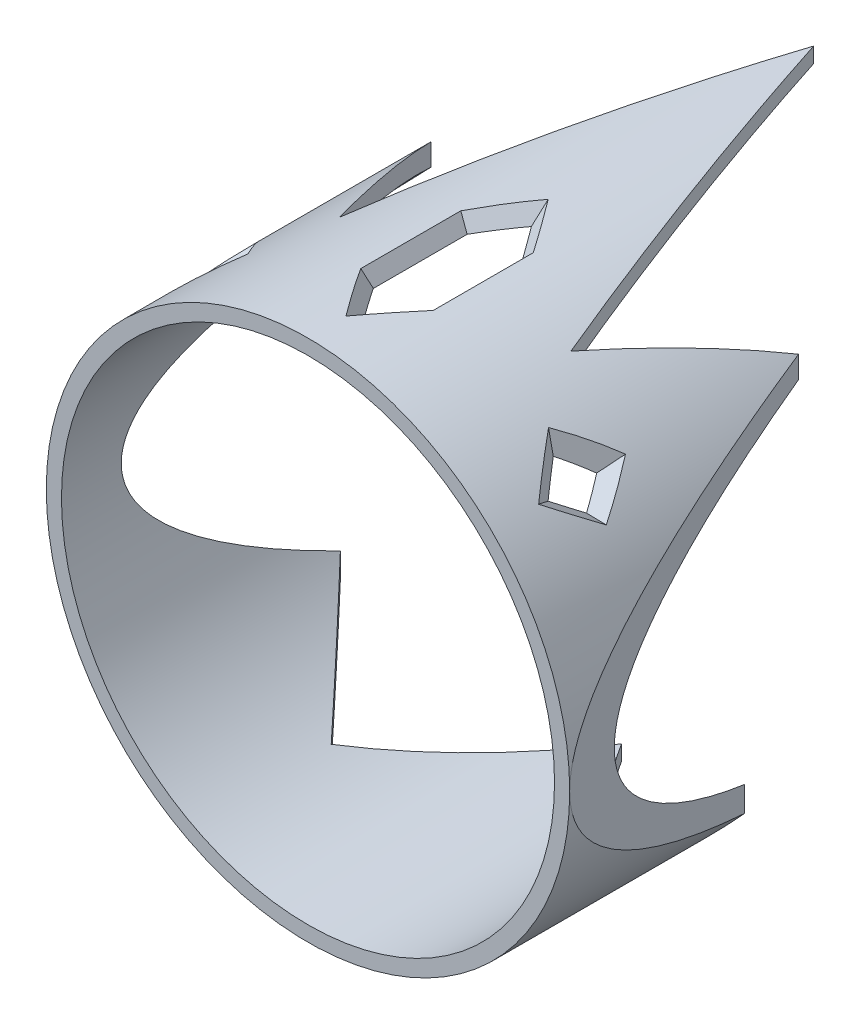
SolidWorks part; units mm, degrees
ref_plane "Alzado" through (0, 0, 0) normal (0, 0, 1) x (1, 0, 0)
ref_plane "Planta" through (0, 0, 0) normal (0, 1, 0) x (1, 0, 0)
ref_plane "Vista lateral" through (0, 0, 0) normal (1, 0, 0) x (0, 0, -1)
sketch "Croquis1" plane through (0, 0, 0) normal (0, 0, 1) x (1, 0, 0)
  circle A0 centre (0, 0) radius 97.5
  circle A1 centre (0, 0) radius 103.5
  dimension "D1" = 195
  dimension "D2" = 6
extrude "Base" add sketch "Croquis1" along normal blind 200
sketch "Croquis2" plane through (0, 0, 0) normal (0, 1, 0) x (1, 0, 0)
  line L3 (-103.5, -200) -> (103.5, -200)
  line L9 (-103.5, -200) -> (-72.7145, -78.6917)
  line L12 (-103.5, 0) -> (103.5, 0)
  line L14 (-72.7145, -78.6917) -> (-45.8128, -141.8175)
  line L15 (-45.8128, -141.8175) -> (0, 0)
  line L16 (0, -110) -> (0, 110) construction
  line L17 (103.5, -200) -> (72.7145, -78.6917)
  line L18 (72.7145, -78.6917) -> (45.8128, -141.8175)
  line L19 (45.8128, -141.8175) -> (0, 0)
  line L20 (-103.5, -200) -> (-103.5, 0)
  line L21 (-103.5, 0) -> (103.5, 0)
  line L22 (103.5, -200) -> (103.5, 0)
  line L24 (-103.5, -200) -> (103.5, -200)
  line L25 (-103.5, -200) -> (-103.5, 0)
  line L26 (-103.5, 0) -> (103.5, 0)
  line L27 (103.5, -200) -> (103.5, 0)
extrude "Diseño" cut sketch "Croquis2" against normal blind 150 and the other way blind 150 contours L20 L9 L14 L15 L12 | L17 L22 L12 L19 L18 region at (-62.7103, 0, 60.8606) region at (62.7103, 0, 60.8606)
ref_plane "Plano1" through (0, -90, 0) normal (0, -1, 0) x (-1, 0, 0)
sketch "Croquis12" plane through (0, -90, 0) normal (0, -1, 0) x (-1, 0, 0)
  line L0 (-103.5, -200) -> (103.5, -200)
  line L1 (0, 0) -> (0, -200) construction
  line L5 (-45.8128, -145.0137) -> (0, -76.0282)
  line L9 (0, -261.1756) -> (0, -77.6489) construction
  line L10 (-103.5, -200) -> (103.5, -200)
  line L11 (-103.5, -200) -> (-103.5, 1.9095)
  line L12 (-103.5, 1.9095) -> (103.5, 1.9095)
  line L13 (103.5, -200) -> (103.5, 1.9095)
  line L14 (-45.8128, -145.0137) -> (-79.9598, -107.2415)
  line L15 (-79.9598, -107.2415) -> (-103.5, -200)
  line L16 (79.9598, -107.2415) -> (103.5, -200)
  line L17 (45.8128, -145.0137) -> (79.9598, -107.2415)
  line L18 (45.8128, -145.0137) -> (0, -76.0282)
  line L19 (-72.7145, -78.6917) -> (-103.5, -200) construction
extrude "PatrónTrasero" cut sketch "Croquis12" against normal blind 90 and the other way blind 20 contours L13 L12 L11 L14 L5 region at (0, -90, 64.361)
ref_plane "Plano2" through (0, 103.5, 0) normal (0, 1, 0) x (1, 0, 0)
ref_plane "Plano3" through (0, 94.5, 0) normal (0, 1, 0) x (1, 0, 0)
sketch "Croquis14" plane through (0, 103.5, 0) normal (0, 1, 0) x (1, 0, 0)
  line L0 (0, 0) -> (0, -200) construction
  line L1 (-103.5, -200) -> (103.5, -200) construction
  line L2 (0, -85) -> (0, -105) construction
  line L4 (15, -165) -> (15, -125)
  line L5 (0, -105) -> (0, -185) construction
  line L7 (0, -105) -> (15, -125)
  line L9 (0, -185) -> (15, -165)
  line L10 (0, -185) -> (-15, -165)
  line L11 (-15, -165) -> (-15, -125)
  line L12 (0, -105) -> (-15, -125)
  dimension "D1" = 15
  dimension "D2" = 20
  dimension "D3" = 20
  dimension "D4" = 40
  dimension "D5" = 15
sketch "Croquis17" plane through (0, 94.5, 0) normal (0, 1, 0) x (1, 0, 0)
  line L0 (-15, -125) -> (0, -105) construction
  line L1 (-9, -127) -> (0, -115)
  line L8 (0, -105) -> (15, -125) construction
  line L9 (15, -125) -> (15, -165) construction
  line L10 (15, -165) -> (0, -185) construction
  line L11 (0, -185) -> (-15, -165) construction
  line L12 (-15, -165) -> (-15, -125) construction
  line L13 (0, -115) -> (9, -127)
  line L14 (9, -127) -> (9, -163)
  line L15 (9, -163) -> (0, -175)
  line L16 (0, -175) -> (-9, -163)
  line L17 (-9, -163) -> (-9, -127)
  dimension "D1" = 6
loft "RanuraPrimalJewel" cut profiles "Croquis14", "Croquis17" connector at (15, 103.5, 165) connector at (9, 94.5, 163)
sketch "Referencia" plane through (0, 0, 0) normal (0, 1, 0) x (1, 0, 0)
  line L0 (0, 34.4265) -> (0, -191.3304) construction
  line L1 (115.64, -78.4519) -> (-152.2306, -78.4519) construction
ref_plane "PlanoRef1" through (0, 0, 0) normal (-0.6374, 0.7705, 0) x (0, 0, 1)
ref_plane "PlanoRef2" through (0, 0, 0) normal (0.6374, 0.7705, 0) x (0, 0, 1)
ref_plane "PlanoJ1" through (-65.9734, 79.7481, 0) normal (-0.6374, 0.7705, 0) x (0, 0, 1)
ref_plane "PlanoJ2" through (-60.2366, 72.8135, 0) normal (-0.6374, 0.7705, 0) x (0, 0, 1)
sketch "Croquis20" plane through (-65.9734, 79.7481, 0) normal (-0.6374, 0.7705, 0) x (0, 0, 1)
  line L0 (78.6917, -9.0789) -> (200, -9.0789) construction
  line L1 (200, -79.7481) -> (200, 103.5) construction
  line L3 (146.6447, -9.0789) -> (164.3223, -26.7566)
  line L4 (164.3223, -26.7566) -> (182, -9.0789)
  line L5 (182, -9.0789) -> (164.3223, 8.5988)
  line L6 (164.3223, 8.5988) -> (146.6447, -9.0789)
  circle A0 centre (164.3223, -9.0789) radius 12.5 construction
  dimension "D1" = 18
  dimension "D2" = 25
sketch "Croquis22" plane through (-60.2366, 72.8135, 0) normal (-0.6374, 0.7705, 0) x (0, 0, 1)
  line L0 (164.3223, -26.7566) -> (182, -9.0789) construction
  line L1 (157.9584, -9.0789) -> (164.3223, -15.4429)
  line L2 (164.3223, -15.4429) -> (170.6863, -9.0789)
  line L3 (170.6863, -9.0789) -> (164.3223, -2.7149)
  line L4 (164.3223, -2.7149) -> (157.9584, -9.0789)
  circle A0 centre (164.3223, -9.0789) radius 4.5 construction
  dimension "D1" = 9
  dimension "D2" = 180
loft "Cortar-Recubrir1" cut profiles "Croquis20", "Croquis22" connector at (-72.9688, 73.961, 146.6447) connector at (-67.232, 67.0264, 157.9584)
ref_plane "PlanoK1" through (65.9734, 79.7481, 0) normal (0.6374, 0.7705, 0) x (0, 0, 1)
ref_plane "PlanoK2" through (60.2366, 72.8135, 0) normal (0.6374, 0.7705, 0) x (0, 0, 1)
sketch "Croquis29" plane through (65.9734, 79.7481, 0) normal (0.6374, 0.7705, 0) x (0, 0, 1)
  line L0 (78.6917, 9.0789) -> (200, 9.0789) construction
  line L1 (200, -103.5) -> (200, 79.7481) construction
  line L3 (182, 9.0789) -> (164.3223, 26.7566)
  line L4 (164.3223, 26.7566) -> (146.6447, 9.0789)
  line L5 (146.6447, 9.0789) -> (164.3223, -8.5988)
  line L6 (164.3223, -8.5988) -> (182, 9.0789)
  circle A0 centre (164.3223, 9.0789) radius 12.5 construction
  dimension "D1" = 18
  dimension "D2" = 25
sketch "Croquis30" plane through (60.2366, 72.8135, 0) normal (0.6374, 0.7705, 0) x (0, 0, 1)
  line L0 (164.3223, 26.7566) -> (146.6447, 9.0789) construction
  line L1 (157.9584, 9.0789) -> (164.3223, 2.7149)
  line L2 (164.3223, 2.7149) -> (170.6863, 9.0789)
  line L3 (170.6863, 9.0789) -> (164.3223, 15.4429)
  line L4 (164.3223, 15.4429) -> (157.9584, 9.0789)
  circle A0 centre (164.3223, 9.0789) radius 4.5 construction
  dimension "D1" = 9
  dimension "D2" = 0
loft "Cortar-Recubrir2" cut profiles "Croquis30", "Croquis29" connector at (67.232, 67.0264, 170.6863) connector at (72.9688, 73.961, 182)
